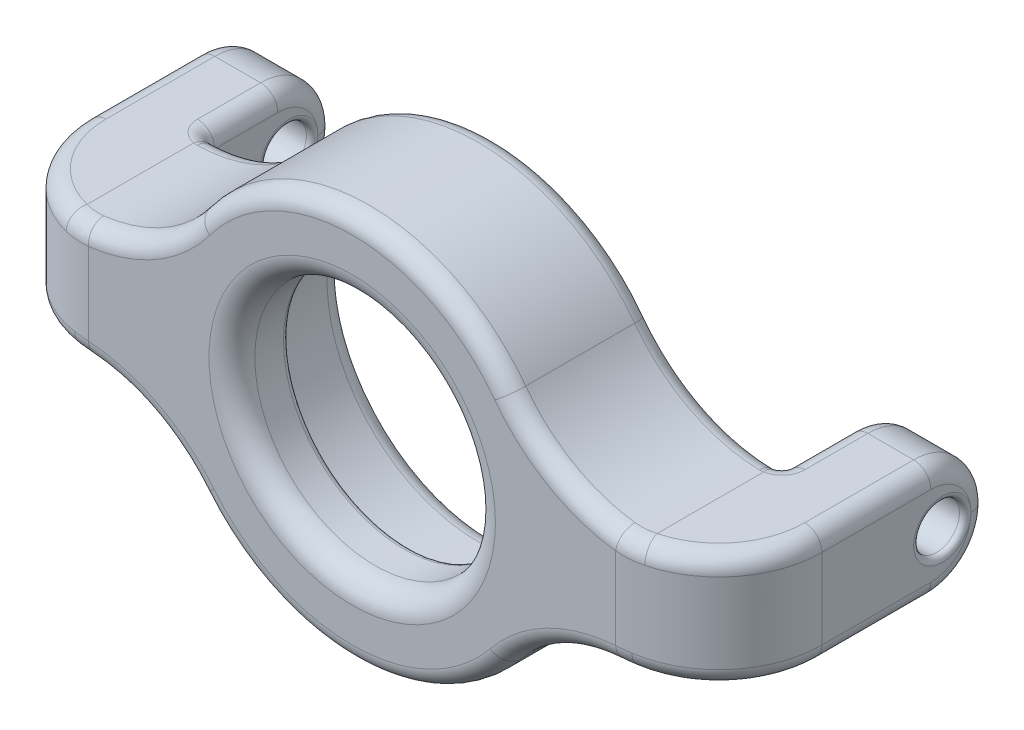
SolidWorks part; units mm, degrees
ref_plane "Płaszczyzna przednia" through (0, 0, 0) normal (0, 0, 1) x (1, 0, 0)
ref_plane "Płaszczyzna górna" through (0, 0, 0) normal (0, 1, 0) x (1, 0, 0)
ref_plane "Płaszczyzna prawa" through (0, 0, 0) normal (1, 0, 0) x (0, 0, -1)
sketch "Szkic1" plane through (0, 0, 0) normal (0, 0, 1) x (1, 0, 0)
  circle A0 centre (0, 0) radius 13.2
  circle A1 centre (0, 0) radius 10.5
extrude "Dodanie-wyciągnięcie1" add sketch "Szkic1" along normal blind 5
sketch "Szkic2" plane through (0, 0, 5) normal (0, 0, 1) x (1, 0, 0)
  circle A0 centre (0, 0) radius 13.2
  circle A1 centre (0, 0) radius 17
extrude "Dodanie-wyciągnięcie2" add sketch "Szkic2" against normal blind 12.5
sketch "Szkic3" plane through (0, 0, 5) normal (0, 0, 1) x (1, 0, 0)
  line L0 (0, 0) -> (0, -0.5)
  line L1 (29, -0.5) -> (-29, -0.5)
  line L2 (-29, -5.5) -> (-29, 4.5)
  line L3 (-29, 4.5) -> (-12, 4.5)
  line L4 (-12, 4.5) -> (-12, -5.5)
  line L5 (-12, -5.5) -> (-29, -5.5)
  line L6 (12, -5.5) -> (29, -5.5)
  line L7 (12, 4.5) -> (12, -5.5)
  line L8 (29, 4.5) -> (12, 4.5)
  line L9 (29, -5.5) -> (29, 4.5)
  point P4 (0, 0)
  point P8 (0, -0.5)
  point P11 (-29, -0.5)
  circle M3 centre (0, 0) radius 17
extrude "Dodanie-wyciągnięcie3" add sketch "Szkic3" against normal blind 12.5 contours L1 L9 L8 M3 | L6 L9 L1 M3 | L3 L2 L1 M3 | L5 L1 L2 M3
sketch "Szkic4" plane through (0, 0, -7.5) normal (0, 0, -1) x (-1, 0, 0)
  line L0 (-16.0857, -5.5) -> (-29, -5.5) construction
  line L1 (-29, 4.5) -> (-25, 4.5)
  line L2 (-29, 4.5) -> (-29, -5.5)
  line L3 (-29, -5.5) -> (-25, -5.5)
  line L4 (-25, 4.5) -> (-25, -5.5)
  line L5 (16.0857, -5.5) -> (29, -5.5) construction
  line L6 (29, 4.5) -> (25, 4.5)
  line L7 (29, 4.5) -> (29, -5.5)
  line L8 (29, -5.5) -> (25, -5.5)
  line L9 (25, 4.5) -> (25, -5.5)
  line L10 (-25, 4.5) -> (-17.8, 4.5)
  line L11 (-29, 4.5) -> (-16.3936, 4.5) construction
  line L13 (-29, 4.5) -> (-32, 4.5)
  line L14 (-29, 4.5) -> (-29, -5.5)
  line L15 (-29, -5.5) -> (-32, -5.5)
  line L16 (-32, 4.5) -> (-32, -5.5)
  line L17 (29, 4.5) -> (32, 4.5)
  line L18 (29, 4.5) -> (29, -5.5)
  line L19 (29, -5.5) -> (32, -5.5)
  line L20 (32, 4.5) -> (32, -5.5)
  line M5 (-16.3936, 4.5) -> (-29, 4.5)
  line M6 (-29, 4.5) -> (-29, -5.5)
  line M7 (-29, -5.5) -> (-16.0857, -5.5)
  line M9 (16.0857, -5.5) -> (29, -5.5)
  line M10 (29, -5.5) -> (29, 4.5)
  line M11 (29, 4.5) -> (16.3936, 4.5)
extrude "Dodanie-wyciągnięcie5" add sketch "Szkic4" along normal blind 11 and the other way up to surface contours L4 M5 M6 M7 | L13 L16 L15 M6 | L20 L17 L19 M10 | L9 M11 M9 M10 other way up to face at (10.5, 0, 5)
sketch "Szkic5" plane through (32, 0, 0) normal (1, 0, 0) x (0, 0, -1)
  line L0 (18.5, 4.5) -> (14.5, 4.5)
  line L1 (-5, 4.5) -> (18.5, 4.5) construction
  line L2 (14.5, 4.5) -> (14.5, -0.5)
  line L3 (18.5, 4.5) -> (18.5, -5.5) construction
  circle A0 centre (14.5, -0.5) radius 2
  dimension "D1" = 4
extrude "Wytnij-wyciągnięcie1" cut sketch "Szkic5" against normal up to surface (64 mm away) up to face at (-32, -0.5, -6.75)
fillet "Zaokrąglenie1" radius 14 4 edges at (16.0857, -5.5, -1.25) (16.3936, 4.5, -1.25) (-16.3936, 4.5, -1.25) (-16.0857, -5.5, -1.25)
fillet "Zaokrąglenie2" radius 5 4 edges at (28.5, -5.5, -18.5) (28.5, 4.5, -18.5) (-28.5, -5.5, -18.5) (-28.5, 4.5, -18.5)
fillet "Zaokrąglenie3" radius 9 2 edges at (32, -0.5, 5) (-32, -0.5, 5)
fillet "Zaokrąglenie4" radius 0.5 8 edges at (13.2, 0, 0) (-25, -0.5, -7.5) (25, -0.5, -7.5) (-25, -0.5, -16.5) (-32, -0.5, -16.5) (32, -0.5, -16.5) (25, -0.5, -16.5) (10.5, 0, 0)
fillet "Zaokrąglenie5" radius 2 1 edges at (10.5, 0, 5)
fillet "Zaokrąglenie7" radius 1.5 45 edges at (24.9676, 4.5, -7.823) (24.744, 4.5006, -7.5636) (18.4217, 6.0759, -7.5) (0, 17, -7.5) (-18.4217, 6.0759, -7.5) (-24.6654, 4.5016, -7.5282) (-24.9676, 4.5, -7.823) (-25, 4.5, -10.75) (-25, 3.0355, -17.0355) (-25, -4.0355, -17.0355) (-25, -5.5, -10.75) (-24.8536, -5.5, -7.6464) (-24.2994, -5.5, -7.5) (-18.0693, -6.8649, -7.5) (0, -17, -7.5) (18.0693, -6.8649, -7.5) (24.2994, -5.5, -7.5) (24.8536, -5.5, -7.6464) (25, -5.5, -10.75) (25, -4.0355, -17.0355) (-32, 4.5, -8.75) (-29.9954, 4.5, 1.6625) (-17.7632, 6.4407, 5) (0, 17, 5) (17.7632, 6.4407, 5) (29.9954, 4.5, 1.6625) (32, 4.5, -8.75) (32, 3.0355, -17.0355) (32, -4.0355, -17.0355) (32, -5.5, -8.75) (29.7412, -5.5, 1.9629) (17.5777, -7.1115, 5) (0, -17, 5) (-17.5777, -7.1115, 5) (-29.7412, -5.5, 1.9629) (-32, -5.5, -8.75) (-32, -4.0355, -17.0355) (25, 4.5, -10.75) (25, 3.0355, -17.0355) (-32, 3.0355, -17.0355) (13.2, 0, -7.5)
